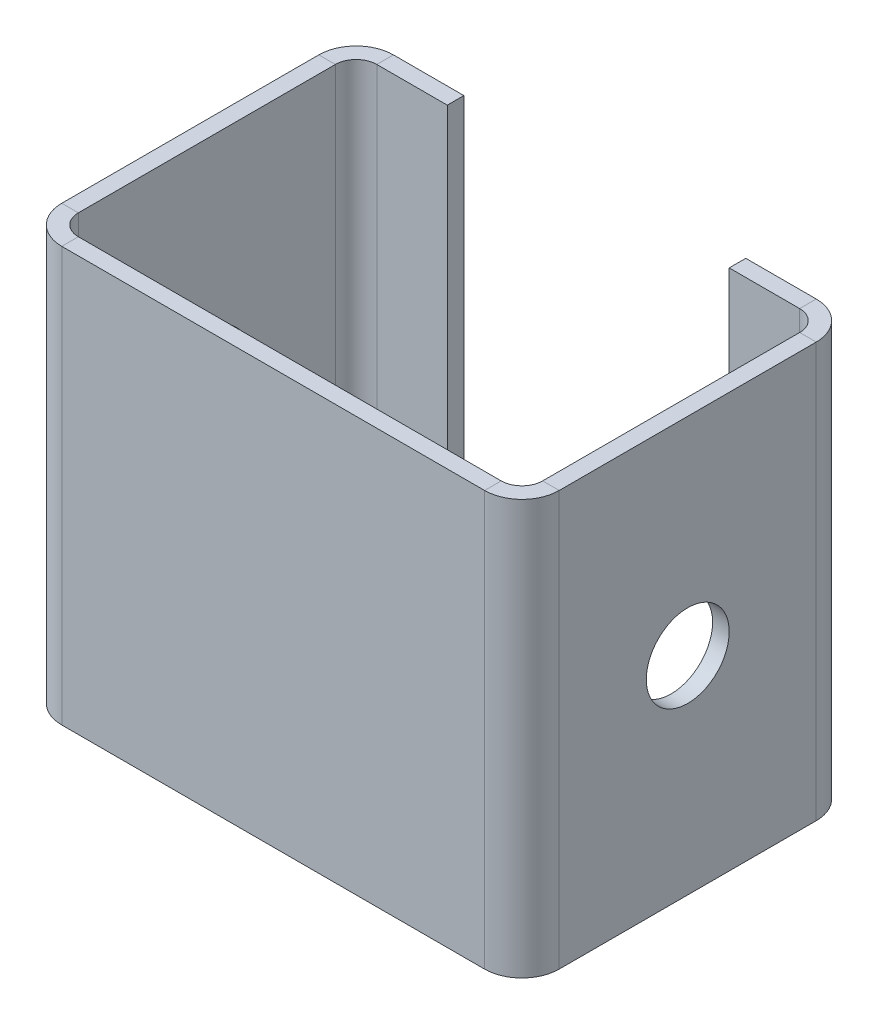
SolidWorks part; units mm, degrees
note: The reader was unsure of these and kept them because the rebuilt part matched: flange length of "Edge-Flange1", "Edge-Flange2".
material "AISI 304"
ref_plane "Front Plane" through (0, 0, 0) normal (0, 0, 1) x (1, 0, 0)
ref_plane "Top Plane" through (0, 0, 0) normal (0, 1, 0) x (1, 0, 0)
ref_plane "Right Plane" through (0, 0, 0) normal (1, 0, 0) x (0, 0, -1)
sketch "Sketch1" plane through (0, 0, 0) normal (0, 0, 1) x (1, 0, 0)
  line L1 (-30, -25) -> (30, -25)
  line L2 (-30, -25) -> (-30, 25)
  line L3 (-30, 25) -> (30, 25)
  line L4 (30, -25) -> (30, 25)
  line L5 (-30, -25) -> (30, 25) construction
  line L6 (-30, 25) -> (30, -25) construction
  point P0 (0, 0)
  dimension "D1" = 50
  dimension "D2" = 60
base flange "Base-Flange1" sketch "Sketch1" thickness 2 reverse thickness direction no parameters "D1"=2.5
edge flange "Edge-Flange1" sketch "Sketch10" flange profiles "Sketch10", "Sketch11" flange angle 90 flange length 40 flange position material inside bend radius 2.5 thickness 2 relief obround parameters "D6"=10, "D8"=1
sketch "Sketch10" plane through (30, 0, -2) normal (-1, 0, 0) x (0, 1, 0)
  line L2 (-25, 0) -> (-25, 38)
  line L3 (-25, 38) -> (25, 38)
  line L4 (25, 38) -> (25, 0)
  line L5 (25, 0) -> (-25, 0) construction
  line L6 (25, 0) -> (-25, 0)
sketch "Sketch11" plane through (-30, 0, -2) normal (1, 0, 0) x (0, -1, 0)
  line L2 (-25, 0) -> (-25, 38)
  line L3 (-25, 38) -> (25, 38)
  line L4 (25, 38) -> (25, 0)
  line L5 (25, 0) -> (-25, 0) construction
  line L6 (25, 0) -> (-25, 0)
bend "EdgeBend1" bend radius 2.5 bend angle 90 parameters "D5"=1
bend "EdgeBend2" bend radius 2.5 bend angle 90 parameters "D5"=2
edge flange "Edge-Flange2" sketch "Sketch16" flange profiles "Sketch16", "Sketch17" flange angle 90 flange length 13 flange position material inside bend radius 2.5 thickness 2 relief obround parameters "D6"=10, "D8"=1
sketch "Sketch16" plane through (28, 0, -40) normal (0, 0, -1) x (0, -1, 0)
  line L2 (-25, 0) -> (-25, 11)
  line L3 (-25, 11) -> (25, 11)
  line L4 (25, 11) -> (25, 0)
  line L7 (-25, 0) -> (25, 0) construction
  line L8 (-25, 0) -> (25, 0)
sketch "Sketch17" plane through (-28, 0, -40) normal (0, 0, -1) x (0, 1, 0)
  line L2 (-25, 0) -> (-25, 11)
  line L3 (-25, 11) -> (25, 11)
  line L4 (25, 11) -> (25, 0)
  line L7 (-25, 0) -> (25, 0) construction
  line L8 (-25, 0) -> (25, 0)
bend "EdgeBend3" bend radius 2.5 bend angle 90 parameters "D5"=3
bend "EdgeBend4" bend radius 2.5 bend angle 90 parameters "D5"=4
sketch "Sketch18" plane through (30, 0, 0) normal (1, 0, 0) x (0, 0, -1)
  line L0 (20, -100) -> (20, 0) construction
  line L1 (15, -100) -> (15, 0)
  line L2 (4.5, 25) -> (35.5, 25) construction
  line L3 (25, -100) -> (25, 0)
  arc A2 (15, -100) -> (25, -100) centre (20, -100) ccw
  arc A3 (25, 0) -> (15, 0) centre (20, 0) ccw
  point P2 (20, -50)
  point P11 (20, 25)
  dimension "D1" = 25
  dimension "D2" = 10
  dimension "D3" = 100
  dimension "D4" = 0
extrude "Cut-Extrude1" [suppressed] cut sketch "Sketch18" against normal through all
sketch "Sketch20" plane through (30, 0, 0) normal (1, 0, 0) x (0, 0, -1)
  line L0 (35.5, -25) -> (4.5, -25) construction
  circle A0 centre (20, 0) radius 5
  point P6 (20, -25)
  dimension "D1" = 10
  dimension "D3" = 25
  dimension "D4" = 0
extrude "Cut-Extrude2" cut sketch "Sketch20" against normal through all normal cut yes
sketch "Bend-Lines1" [suppressed] plane through (0, 0, 0) normal (0, 1, 0) x (1, 0, 0)
sketch "Bounding-Box1" [suppressed] plane through (0, 0, 0) normal (0, 1, 0) x (1, 0, 0)
sheet metal parameters "Sheet-Metal1" thickness 2 parameters "D1"=2.5
flat pattern "Flat-Pattern1" [suppressed]
sketch "Bend-Lines2" plane through (0, 0, 0) normal (0, 1, 0) x (1, 0, 0)
sketch3d "Bounding-Box2" [suppressed]
  line L0 (-20, 1400, 0) -> (-20, -1400, 0) construction
  line L1 (20, 1400, 0) -> (20, -1400, 0) construction
  line L2 (-20, 1400, 0) -> (20, 1400, 0) construction
  line L3 (-20, -1400, 0) -> (20, -1400, 0) construction
sheet metal parameters "Sheet-Metal2" thickness 2 parameters "D1"=2.5
flat pattern "Flat-Pattern1"
sketch "Bend-Lines2" plane through (0, 0, 0) normal (0, 0, 1) x (1, 0, 0)
  line L0 (-18.0918, 1400) -> (-18.0918, -1400) construction
  line L1 (18.0918, -1400) -> (18.0918, 1400) construction
  line L2 (-18.0918, 1400) -> (-18.0918, -1400) construction
  line L3 (18.0918, -1400) -> (18.0918, 1400) construction
sketch3d "Bounding-Box2" [suppressed]
  line L0 (46.1836, 1400, 0) -> (46.1836, -1400, 0) construction
  line L1 (-46.1836, 1400, 0) -> (-46.1836, -1400, 0) construction
  line L2 (46.1836, 1400, 0) -> (-46.1836, 1400, 0) construction
  line L3 (46.1836, -1400, 0) -> (-46.1836, -1400, 0) construction
bend of the flat pattern "Flatten-<EdgeBend1>1"
bend of the flat pattern "Flatten-<EdgeBend2>1"
sheet metal parameters "Sheet-Metal3" thickness 2 parameters "D1"=2.5
flat pattern "Flat-Pattern1" [suppressed]
sketch "Bend-Lines2" plane through (0, 0, 0) normal (0, 0, 1) x (1, 0, 0)
  line L0 (-15.5918, 150) -> (-15.5918, -150) construction
  line L1 (15.5918, -150) -> (15.5918, 150) construction
  line L2 (-15.5918, 150) -> (-15.5918, -150) construction
  line L3 (15.5918, -150) -> (15.5918, 150) construction
  line L4 (-36.7754, 150) -> (-36.7754, -150) construction
  line L5 (36.7754, -150) -> (36.7754, 150) construction
  line L6 (-36.7754, 150) -> (-36.7754, -150) construction
  line L7 (36.7754, -150) -> (36.7754, 150) construction
sketch3d "Bounding-Box2" [suppressed]
  line L0 (49.8673, 150, 0) -> (49.8673, -150, 0) construction
  line L1 (-49.8673, 150, 0) -> (-49.8673, -150, 0) construction
  line L2 (49.8673, 150, 0) -> (-49.8673, 150, 0) construction
  line L3 (49.8673, -150, 0) -> (-49.8673, -150, 0) construction
bend of the flat pattern "Flatten-<EdgeBend1>1"
bend of the flat pattern "Flatten-<EdgeBend2>1"
bend of the flat pattern "Flatten-<EdgeBend3>1"
bend of the flat pattern "Flatten-<EdgeBend4>1"
sketch "Sketch18-1" [suppressed] plane through (13.6836, 0, 0) normal (0, 0, 1) x (1, 0, 0)
  line L0 (12.5, -135) -> (12.5, -35) construction
  line L1 (7.5, -135) -> (7.5, -35)
  line L3 (17.5, -135) -> (17.5, -35)
  line L4 (36.1836, -150) -> (-63.5509, -150) construction
  line L5 (0, -150) -> (0, 150) construction
  arc A2 (7.5, -135) -> (17.5, -135) centre (12.5, -135) ccw
  arc A3 (17.5, -35) -> (7.5, -35) centre (12.5, -35) ccw
  point P2 (12.5, -85)
  dimension "D1" = 15
  dimension "D2" = 10
  dimension "D3" = 100
  dimension "D4" = 12.5
sheet metal parameters "Sheet-Metal6" thickness 2 parameters "D1"=2.5
flat pattern "Flat-Pattern1" [suppressed]
sketch "Bend-Lines2" plane through (0, 0, 0) normal (0, 0, 1) x (1, 0, 0)
  line L0 (-15.5918, 150) -> (-15.5918, -150) construction
  line L1 (15.5918, -150) -> (15.5918, 150) construction
  line L2 (-15.5918, 150) -> (-15.5918, -150) construction
  line L3 (15.5918, -150) -> (15.5918, 150) construction
  line L4 (-36.7754, 150) -> (-36.7754, -150) construction
  line L5 (36.7754, -150) -> (36.7754, 150) construction
  line L6 (-36.7754, 150) -> (-36.7754, -150) construction
  line L7 (36.7754, -150) -> (36.7754, 150) construction
sketch3d "Bounding-Box2" [suppressed]
  line L0 (49.8673, 150, 0) -> (49.8673, -150, 0) construction
  line L1 (-49.8673, 150, 0) -> (-49.8673, -150, 0) construction
  line L2 (49.8673, 150, 0) -> (-49.8673, 150, 0) construction
  line L3 (49.8673, -150, 0) -> (-49.8673, -150, 0) construction
bend of the flat pattern "Flatten-<EdgeBend1>1"
bend of the flat pattern "Flatten-<EdgeBend2>1"
bend of the flat pattern "Flatten-<EdgeBend3>1"
bend of the flat pattern "Flatten-<EdgeBend4>1"
sketch "Sketch18-1" [suppressed] plane through (13.6836, 0, 0) normal (0, 0, 1) x (1, 0, 0)
  line L0 (12.5, 25) -> (12.5, 125) construction
  line L1 (7.5, 25) -> (7.5, 125)
  line L2 (-63.5509, 150) -> (36.1836, 150) construction
  line L3 (17.5, 25) -> (17.5, 125)
  line L5 (0, -150) -> (0, 150) construction
  arc A2 (7.5, 25) -> (17.5, 25) centre (12.5, 25) ccw
  arc A3 (17.5, 125) -> (7.5, 125) centre (12.5, 125) ccw
  point P2 (12.5, 75)
  dimension "D1" = 25
  dimension "D2" = 10
  dimension "D3" = 100
  dimension "D4" = 12.5
sheet metal parameters "Sheet-Metal7" thickness 2 parameters "D1"=2.5
flat pattern "Flat-Pattern1" [suppressed]
sketch "Bend-Lines2" plane through (0, 0, 0) normal (0, 0, 1) x (1, 0, 0)
  line L0 (-28.0918, 25) -> (-28.0918, -25) construction
  line L1 (28.0918, -25) -> (28.0918, 25) construction
  line L2 (-28.0918, 25) -> (-28.0918, -25) construction
  line L3 (28.0918, -25) -> (28.0918, 25) construction
  line L4 (-64.2754, 25) -> (-64.2754, -25) construction
  line L5 (64.2754, -25) -> (64.2754, 25) construction
  line L6 (-64.2754, 25) -> (-64.2754, -25) construction
  line L7 (64.2754, -25) -> (64.2754, 25) construction
sketch3d "Bounding-Box2" [suppressed]
  line L0 (-75.3673, -25, 0) -> (75.3673, -25, 0) construction
  line L1 (-75.3673, 25, 0) -> (75.3673, 25, 0) construction
  line L2 (-75.3673, -25, 0) -> (-75.3673, 25, 0) construction
  line L3 (75.3673, -25, 0) -> (75.3673, 25, 0) construction
bend of the flat pattern "Flatten-<EdgeBend1>1"
bend of the flat pattern "Flatten-<EdgeBend2>1"
bend of the flat pattern "Flatten-<EdgeBend3>1"
bend of the flat pattern "Flatten-<EdgeBend4>1"
sketch "Sketch18-1" plane through (26.1836, 0, 0) normal (0, 0, 1) x (1, 0, 0)
  line L0 (20, -100) -> (20, 0) construction
  line L1 (15, -100) -> (15, 0)
  line L2 (-101.5509, 25) -> (49.1836, 25) construction
  line L3 (25, -100) -> (25, 0)
  arc A2 (15, -100) -> (25, -100) centre (20, -100) ccw
  arc A3 (25, 0) -> (15, 0) centre (20, 0) ccw
  point P2 (20, -50)
  dimension "D1" = 25
  dimension "D2" = 10
  dimension "D3" = 100
